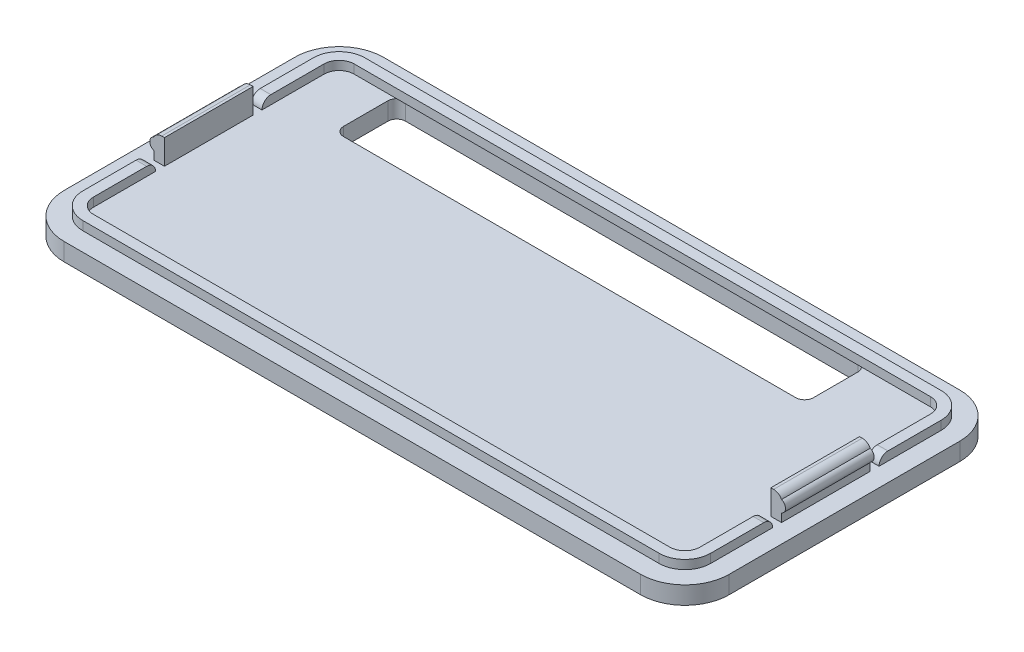
SolidWorks part; units mm, degrees
ref_plane "前视基准面" through (0, 0, 0) normal (0, 0, 1) x (1, 0, 0)
ref_plane "上视基准面" through (0, 0, 0) normal (0, 1, 0) x (1, 0, 0)
ref_plane "右视基准面" through (0, 0, 0) normal (1, 0, 0) x (0, 0, -1)
sketch "zero" plane through (0, 0, 0) normal (0, 1, 0) x (1, 0, 0)
  line L1 (-29.5, 15) -> (29.5, 15)
  line L2 (-32.5, 12) -> (-32.5, -12)
  line L3 (-29.5, -15) -> (29.5, -15)
  line L4 (32.5, 12) -> (32.5, -12)
  line L5 (-32.5, 15) -> (32.5, -15) construction
  line L6 (-32.5, -15) -> (32.5, 15) construction
  line L7 (-25.7, -15) -> (-14.5, -15)
  line L8 (-25.7, -15) -> (-25.7, -9.6569)
  line L9 (-25.7, -9.6569) -> (-14.5, -9.6569)
  line L10 (-14.5, -15) -> (-14.5, -9.6569)
  line L11 (5.2, -15) -> (12.7, -15)
  line L12 (5.2, -15) -> (5.2, -11)
  line L13 (5.2, -11) -> (12.7, -11)
  line L14 (12.7, -15) -> (12.7, -11)
  line L15 (17.8, -15) -> (25.3, -15)
  line L16 (17.8, -15) -> (17.8, -11)
  line L17 (17.8, -11) -> (25.3, -11)
  line L18 (25.3, -15) -> (25.3, -11)
  line L19 (-32.5, 7.7) -> (-19.5, 7.7)
  line L20 (-32.5, 7.7) -> (-32.5, -4.3)
  line L21 (-32.5, -4.3) -> (-19.5, -4.3)
  line L22 (-19.5, 7.7) -> (-19.5, -4.3)
  line L23 (-25.5, 14) -> (25.5, 14)
  line L24 (-25.5, 14) -> (-25.5, 8.8)
  line L25 (-25.5, 8.8) -> (25.5, 8.8)
  line L26 (25.5, 14) -> (25.5, 8.8)
  line L27 (-19.5, 7.2329) -> (-35.5, 7.2329)
  line L28 (-19.5, 7.2329) -> (-19.5, -3.7671)
  line L29 (-19.5, -3.7671) -> (-35.5, -3.7671)
  line L30 (-35.5, 7.2329) -> (-35.5, -3.7671)
  arc A0 (29.5, -15) -> (32.5, -12) centre (29.5, -12) ccw
  arc A1 (29.5, 15) -> (32.5, 12) centre (29.5, 12) cw
  arc A2 (-32.5, -12) -> (-29.5, -15) centre (-29.5, -12) ccw
  arc A3 (-29.5, 15) -> (-32.5, 12) centre (-29.5, 12) ccw
  circle A4 centre (-29, 11.4) radius 3
  circle A5 centre (-29, -11.5) radius 3
  circle A6 centre (29, 11.4) radius 3
  circle A7 centre (29, -11.5) radius 3
  circle A8 centre (-29, 11.4) radius 1.375
  circle A9 centre (-29, -11.5) radius 1.375
  circle A10 centre (29, -11.5) radius 1.375
  circle A11 centre (29, 11.4) radius 1.375
  point P0 (0, 0)
  dimension "D3" = 3
  dimension "D4" = 6
  dimension "D9" = 2.75
  dimension "D1" = 65
  dimension "D2" = 30
  dimension "D5" = 3.6
  dimension "D6" = 3.5
  dimension "D7" = 3.5
  dimension "D8" = 3.5
  dimension "D10" = 12
  dimension "D11" = 7.3
  dimension "D12" = 13
  dimension "D13" = 11.2
  dimension "D14" = 6.8
  dimension "D15" = 19.7
  dimension "D16" = 7.5
  dimension "D17" = 7.5
  dimension "D18" = 5.1
  dimension "D19" = 4
  dimension "D20" = 5.2
  dimension "D21" = 7
  dimension "D22" = 7
  dimension "D23" = 1
  dimension "D24" = 11
  dimension "D25" = 16
sketch "sugar" plane through (0, 0, 0) normal (0, 1, 0) x (1, 0, 0)
  line L1 (-29.5, 15) -> (29.5, 15)
  line L2 (-32.5, 12) -> (-32.5, -12)
  line L3 (-29.5, -15) -> (29.5, -15)
  line L4 (32.5, 12) -> (32.5, -12)
  line L5 (-32.5, 15) -> (32.5, -15) construction
  line L6 (-32.5, -15) -> (32.5, 15) construction
  line L7 (23.5, -11.5) -> (19.5, -11.5)
  line L8 (23.5, -11.5) -> (23.5, -13.9082)
  line L9 (23.5, -13.9082) -> (19.5, -13.9082)
  line L10 (19.5, -11.5) -> (19.5, -13.9082)
  line L11 (16, -11.0071) -> (8.5, -11.0071)
  line L12 (16, -11.0071) -> (16, -15)
  line L13 (16, -15) -> (8.5, -15)
  line L14 (8.5, -11.0071) -> (8.5, -15)
  line L15 (20.5, -13.9082) -> (22.5, -13.9082)
  line L16 (20.5, -13.9082) -> (20.5, -14.8173)
  line L17 (20.5, -14.8173) -> (22.5, -14.8173)
  line L18 (22.5, -13.9082) -> (22.5, -14.8173)
  arc A0 (29.5, 15) -> (32.5, 12) centre (29.5, 12) cw
  arc A1 (29.5, -15) -> (32.5, -12) centre (29.5, -12) ccw
  arc A2 (-32.5, -12) -> (-29.5, -15) centre (-29.5, -12) ccw
  arc A3 (-29.5, 15) -> (-32.5, 12) centre (-29.5, 12) ccw
  circle A4 centre (-29, 11.4) radius 3
  circle A5 centre (-29, 11.4) radius 1.375
  circle A6 centre (-29, -11.5) radius 3
  circle A7 centre (-29, -11.5) radius 1.375
  circle A8 centre (29, 11.4) radius 3
  circle A9 centre (29, 11.4) radius 1.375
  circle A10 centre (29, -11.5) radius 3
  circle A11 centre (29, -11.5) radius 1.375
  dimension "D3" = 3
  dimension "D1" = 65
  dimension "D2" = 30
  dimension "D4" = 9
  dimension "D5" = 4
  dimension "D6" = 3.5
  dimension "D7" = 7.5
  dimension "D8" = 2
  dimension "D9" = 1
sketch "case" plane through (0, 0, 0) normal (0, 1, 0) x (1, 0, 0)
  line L1 (-34.0422, 18) -> (30.9578, 18)
  line L2 (-39.0422, 13) -> (-39.0422, -13)
  line L3 (-34.0422, -18) -> (30.9578, -18)
  line L4 (35.9578, 13) -> (35.9578, -13)
  line L5 (-39.0422, 18) -> (35.9578, -18) construction
  line L6 (-39.0422, -18) -> (35.9578, 18) construction
  arc A0 (-39.0422, -13) -> (-34.0422, -18) centre (-34.0422, -13) ccw
  arc A1 (30.9578, -18) -> (35.9578, -13) centre (30.9578, -13) ccw
  arc A2 (30.9578, 18) -> (35.9578, 13) centre (30.9578, 13) cw
  arc A3 (-34.0422, 18) -> (-39.0422, 13) centre (-34.0422, 13) ccw
  point P0 (-1.5422, 0)
  point P3 (-1.5422, 0)
  dimension "D3" = 5
  dimension "D1" = 75
  dimension "D2" = 36
extrude "凸台-拉伸2" add sketch "case" along normal blind 2
sketch "草图2" plane through (0, 0, 0) normal (0, 1, 0) x (1, 0, 0)
  line L4 (-34.0422, -14.7) -> (30.9578, -14.7)
  line L5 (32.6578, -13) -> (32.6578, 13)
  line L6 (30.9578, 14.7) -> (-34.0422, 14.7)
  line L7 (-35.7422, 13) -> (-35.7422, -13)
  line L8 (33.8578, -13) -> (33.8578, 13)
  line L9 (30.9578, 15.9) -> (-34.0422, 15.9)
  line L10 (-36.9422, 13) -> (-36.9422, -13)
  line L11 (-34.0422, -15.9) -> (30.9578, -15.9)
  line L12 (33.8578, -13) -> (33.8578, 13)
  line L13 (30.9578, 15.9) -> (-34.0422, 15.9)
  line L14 (-36.9422, 13) -> (-36.9422, -13)
  line L15 (-34.0422, -15.9) -> (30.9578, -15.9)
  arc A4 (30.9578, -14.7) -> (32.6578, -13) centre (30.9578, -13) ccw
  arc A5 (32.6578, 13) -> (30.9578, 14.7) centre (30.9578, 13) ccw
  arc A6 (-34.0422, 14.7) -> (-35.7422, 13) centre (-34.0422, 13) ccw
  arc A7 (-35.7422, -13) -> (-34.0422, -14.7) centre (-34.0422, -13) ccw
  arc A8 (30.9578, -15.9) -> (33.8578, -13) centre (30.9578, -13) ccw
  arc A9 (33.8578, 13) -> (30.9578, 15.9) centre (30.9578, 13) ccw
  arc A10 (-34.0422, 15.9) -> (-36.9422, 13) centre (-34.0422, 13) ccw
  arc A11 (-36.9422, -13) -> (-34.0422, -15.9) centre (-34.0422, -13) ccw
  arc A12 (30.9578, -15.9) -> (33.8578, -13) centre (30.9578, -13) ccw
  arc A13 (33.8578, 13) -> (30.9578, 15.9) centre (30.9578, 13) ccw
  arc A14 (-34.0422, 15.9) -> (-36.9422, 13) centre (-34.0422, 13) ccw
  arc A15 (-36.9422, -13) -> (-34.0422, -15.9) centre (-34.0422, -13) ccw
  dimension "D1" = 2.1
  dimension "D2" = 1.2
ref_plane "基准面1" through (0, 2, 0) normal (0, 1, 0) x (1, 0, 0)
sketch "草图3" plane through (0, 2, 0) normal (0, 1, 0) x (1, 0, 0)
  line L4 (-34.0422, -14.7) -> (30.9578, -14.7)
  line L5 (32.6578, -13) -> (32.6578, 13)
  line L6 (30.9578, 14.7) -> (-34.0422, 14.7)
  line L7 (-35.7422, 13) -> (-35.7422, -13)
  line L8 (-34.0422, -14.7) -> (30.9578, -14.7)
  line L9 (32.6578, -13) -> (32.6578, 13)
  line L10 (30.9578, 14.7) -> (-34.0422, 14.7)
  line L11 (-35.7422, 13) -> (-35.7422, -13)
  line L12 (-36.9422, 13) -> (-36.9422, -13)
  line L13 (-34.0422, -15.9) -> (30.9578, -15.9)
  line L14 (33.8578, -13) -> (33.8578, 13)
  line L15 (30.9578, 15.9) -> (-34.0422, 15.9)
  line L16 (-36.9422, 13) -> (-36.9422, -13)
  line L17 (-34.0422, -15.9) -> (30.9578, -15.9)
  line L18 (33.8578, -13) -> (33.8578, 13)
  line L19 (30.9578, 15.9) -> (-34.0422, 15.9)
  arc A4 (30.9578, -14.7) -> (32.6578, -13) centre (30.9578, -13) ccw
  arc A5 (32.6578, 13) -> (30.9578, 14.7) centre (30.9578, 13) ccw
  arc A6 (-34.0422, 14.7) -> (-35.7422, 13) centre (-34.0422, 13) ccw
  arc A7 (-35.7422, -13) -> (-34.0422, -14.7) centre (-34.0422, -13) ccw
  arc A8 (30.9578, -14.7) -> (32.6578, -13) centre (30.9578, -13) ccw
  arc A9 (32.6578, 13) -> (30.9578, 14.7) centre (30.9578, 13) ccw
  arc A10 (-34.0422, 14.7) -> (-35.7422, 13) centre (-34.0422, 13) ccw
  arc A11 (-35.7422, -13) -> (-34.0422, -14.7) centre (-34.0422, -13) ccw
  arc A12 (-36.9422, -13) -> (-34.0422, -15.9) centre (-34.0422, -13) ccw
  arc A13 (30.9578, -15.9) -> (33.8578, -13) centre (30.9578, -13) ccw
  arc A14 (33.8578, 13) -> (30.9578, 15.9) centre (30.9578, 13) ccw
  arc A15 (-34.0422, 15.9) -> (-36.9422, 13) centre (-34.0422, 13) ccw
  arc A16 (-36.9422, -13) -> (-34.0422, -15.9) centre (-34.0422, -13) ccw
  arc A17 (30.9578, -15.9) -> (33.8578, -13) centre (30.9578, -13) ccw
  arc A18 (33.8578, 13) -> (30.9578, 15.9) centre (30.9578, 13) ccw
  arc A19 (-34.0422, 15.9) -> (-36.9422, 13) centre (-34.0422, 13) ccw
  dimension "D1" = 0
  dimension "D2" = 0
extrude "凸台-拉伸4" add sketch "草图3" along normal blind 1
ref_plane "基准面3" through (33.8578, 0, 0) normal (1, 0, 0) x (0, 0, -1)
sketch "草图7" plane through (0, 2, 0) normal (0, 1, 0) x (1, 0, 0)
  line L0 (-36.9422, 13) -> (-36.9422, -13) construction
  line L1 (-36.9422, 5) -> (-35.7422, 5)
  line L2 (-36.9422, 5) -> (-36.9422, -5)
  line L3 (-36.9422, -5) -> (-35.7422, -5)
  line L4 (-35.7422, 5) -> (-35.7422, -5)
  line L5 (-35.7422, 13) -> (-35.7422, -13) construction
  point P10 (-35.7422, 0)
  dimension "D1" = 5
  dimension "D2" = 10
extrude "凸台-拉伸8" add sketch "草图7" along normal blind 2.8
ref_plane "基准面5" through (0, 0, 5) normal (0, 0, 1) x (1, 0, 0)
sketch "草图8" plane through (0, 0, 5) normal (0, 0, 1) x (1, 0, 0)
  line L0 (-34.0422, 2) -> (-39.0422, 2) construction
  line L1 (-36.9422, 4.8) -> (-36.9422, 3) construction
  circle A0 centre (-36.6922, 3.6) radius 0.7
  dimension "D1" = 1.4
  dimension "D2" = 1.6
  dimension "D3" = 0.25
extrude "凸台-拉伸9" add sketch "草图8" against normal blind 10
fillet "圆角1" radius 1 1 edges at (-36.9422, 4.8, 0)
ref_plane "基准面7" through (-36.9422, 0, 0) normal (-1, 0, 0) x (0, 0, 1)
sketch "草图11" plane through (-36.9422, 0, 0) normal (-1, 0, 0) x (0, 0, 1)
  line L0 (-13, 2) -> (13, 2) construction
  line L1 (5, 3) -> (6, 3)
  line L2 (5, 3) -> (5, 2)
  line L3 (5, 2) -> (6, 2)
  line L4 (6, 3) -> (6, 2)
  line L6 (-5, 3) -> (-6, 3)
  line L7 (-5, 3) -> (-5, 2)
  line L8 (-5, 2) -> (-6, 2)
  line L9 (-6, 3) -> (-6, 2)
  dimension "D1" = 1
  dimension "D2" = 1
extrude "切除-拉伸1" cut sketch "草图11" against normal blind 1.2
fillet "圆角2" radius 1 2 edges at (-36.3422, 3, 6) (-36.3422, 3, -6)
ref_plane "基准面8" through (0, 0, 0) normal (0, -1, 0) x (-1, 0, 0)
sketch "草图12" plane through (0, 0, 0) normal (0, -1, 0) x (-1, 0, 0)
  line L76 (34.0422, -18) -> (-30.9578, -18) construction
  line L78 (39.0422, 13) -> (39.0422, -13) construction
  line B0 (-8.1993, 1.426) -> (-9.0198, 1.899)
  line B1 (-9.0198, 1.899) -> (-13.2767, 4.3551)
  line B2 (-13.2767, 4.3551) -> (-14.0973, 4.8339)
  line B3 (-15.8183, 4.8339) -> (-16.6389, 4.3551)
  line B4 (-16.6389, 4.3551) -> (-20.8958, 1.899)
  line B5 (-20.8958, 1.899) -> (-21.7165, 1.426)
  line B6 (-22.577, -0.0613) -> (-22.577, -6.8769)
  line B7 (-21.7165, -8.3643) -> (-20.8958, -8.8373)
  line B8 (-20.8958, -8.8373) -> (-16.6389, -11.2934)
  line B9 (-16.6389, -11.2934) -> (-15.8183, -11.772)
  line B10 (-14.0973, -11.772) -> (-13.2767, -11.2934)
  line B11 (-13.2767, -11.2934) -> (-9.0198, -8.8373)
  line B12 (-9.0198, -8.8373) -> (-8.1993, -8.3643)
  line B13 (-7.3388, -6.8769) -> (-7.3388, -0.0613)
  line B14 (-20.6223, 0.7479) -> (-15.3568, 3.791)
  line B15 (-14.5532, 3.791) -> (-9.3162, 0.7422)
  line B16 (-9.3105, 0.0413) -> (-14.3993, -3.0018)
  line B17 (-12.8208, -8.1591) -> (-13.4135, -8.4896)
  line B18 (-13.4705, -8.5865) -> (-13.4705, -10.2961)
  line B19 (-13.5274, -10.393) -> (-14.633, -11.0198)
  line B20 (-14.7983, -10.9229) -> (-14.7983, -5.646)
  line B21 (-14.7413, -5.5491) -> (-12.8607, -4.4835)
  line B22 (-8.9173, -7.8058) -> (-10.0114, -8.4269)
  line B23 (-10.1767, -8.3301) -> (-10.1767, -5.8169)
  line B24 (-10.1197, -5.7201) -> (-9.0256, -5.1046)
  line B25 (-8.8603, -5.2015) -> (-8.8603, -7.7089)
  line B26 (-12.8893, -7.1447) -> (-13.4135, -7.4069)
  line B27 (-13.4705, -7.2872) -> (-13.4705, -5.9423)
  line B28 (-13.4135, -5.8455) -> (-12.9234, -5.5719)
  line B29 (-3.344, -0.54) -> (-5.2189, -0.54)
  line B30 (-5.2189, -0.54) -> (-5.2189, -7.1048)
  line B31 (-5.2189, -7.1048) -> (-4.3868, -7.1048)
  line B32 (-4.3868, -7.1048) -> (-4.3868, -4.5005)
  line B33 (-4.3868, -4.5005) -> (-3.2984, -4.5005)
  line B34 (-3.4066, -3.8281) -> (-4.3868, -3.8281)
  line B35 (-4.3868, -3.8281) -> (-4.3868, -1.2124)
  line B36 (-4.3868, -1.2124) -> (-3.4408, -1.2124)
  line B37 (0.1948, -2.2382) -> (0.1948, -7.1048)
  line B38 (0.1948, -7.1048) -> (1.0098, -7.1048)
  line B39 (1.0098, -7.1048) -> (1.0098, -2.2382)
  line B40 (1.0098, -2.2382) -> (0.1948, -2.2382)
  line B41 (5.7169, -3.3153) -> (4.8849, -2.9847)
  line B42 (6.0417, -2.1983) -> (6.8396, -1.1953)
  line B43 (3.6084, -4.1586) -> (4.4575, -4.5177)
  line B44 (2.9074, -5.1673) -> (2.0014, -6.2729)
  line B45 (10.8229, -2.0102) -> (10.8229, -5.3497)
  line B46 (9.3811, -4.9621) -> (9.3811, -2.0102)
  line B47 (9.3811, -2.0102) -> (7.7912, -2.0102)
  line B48 (7.7912, -2.0102) -> (7.7912, -5.1616)
  line B49 (10.9711, -6.4039) -> (11.0052, -6.4039)
  line B50 (11.0052, -6.4039) -> (11.1193, -7.1048)
  line B51 (11.1193, -7.1048) -> (12.4185, -7.1048)
  line B52 (12.4185, -7.1048) -> (12.4185, -2.0102)
  line B53 (12.4185, -2.0102) -> (10.8229, -2.0102)
  line B54 (16.2708, -6.1019) -> (15.4673, -6.1019)
  line B55 (17.365, -3.1614) -> (18.1513, -3.1614)
  line B56 (18.1513, -3.1614) -> (18.1513, -2.0102)
  line B57 (18.1513, -2.0102) -> (16.2822, -2.0102)
  line B58 (14.0312, -5.0533) -> (14.0312, -5.0875)
  line B59 (13.9344, -6.9168) -> (13.9344, -6.9624)
  line B60 (15.4844, -7.3214) -> (15.9688, -7.3214)
  line B61 (18.6072, -2.5516) -> (19.1657, -3.6002)
  line B62 (21.411, -6.592) -> (21.4508, -6.592)
  line B63 (21.4508, -6.592) -> (21.5648, -7.1048)
  line B64 (21.5648, -7.1048) -> (22.8641, -7.1048)
  line B65 (22.8641, -7.1048) -> (22.8641, -4.2099)
  line B66 (21.2685, -4.7741) -> (21.2685, -5.589)
  line B67 (25.3545, -2.8935) -> (25.3203, -2.8935)
  line B68 (25.3203, -2.8935) -> (25.212, -2.0102)
  line B69 (25.212, -2.0102) -> (23.9127, -2.0102)
  line B70 (23.9127, -2.0102) -> (23.9127, -7.1048)
  line B71 (23.9127, -7.1048) -> (25.4969, -7.1048)
  line B72 (25.4969, -7.1048) -> (25.4969, -4.1928)
  line B73 (27.1552, -3.3608) -> (27.423, -1.9875)
  line B74 (-13.4135, -7.4069) -> (-13.4135, -8.4896)
  line B75 (-13.4705, -7.2872) -> (-13.4705, -8.5865)
  spline B76 degree 3 poles (-14.0973, 4.8339) (-14.3652, 4.982) (-14.6615, 5.0618) (-14.9578, 5.0618) knots 3 3 3 3 4 4 4 4
  spline B77 degree 3 poles (-14.9578, 5.0618) (-15.2541, 5.0618) (-15.5505, 4.982) (-15.8183, 4.8339) knots 4 4 4 4 5 5 5 5
  spline B78 degree 3 poles (-21.7165, 1.426) (-22.2464, 1.1183) (-22.577, 0.5485) (-22.577, -0.0613) knots 8 8 8 8 9 9 9 9
  spline B79 degree 3 poles (-22.577, -6.8769) (-22.577, -7.4923) (-22.2464, -8.0565) (-21.7165, -8.3643) knots 10 10 10 10 11 11 11 11
  spline B80 degree 3 poles (-15.8183, -11.772) (-15.5505, -11.9259) (-15.2541, -12) (-14.9578, -12) knots 14 14 14 14 15 15 15 15
  spline B81 degree 3 poles (-14.9578, -12) (-14.6615, -12) (-14.3652, -11.9259) (-14.0973, -11.772) knots 15 15 15 15 16 16 16 16
  spline B82 degree 3 poles (-8.1993, -8.3643) (-7.6636, -8.0565) (-7.3388, -7.4923) (-7.3388, -6.8769) knots 19 19 19 19 20 20 20 20
  spline B83 degree 3 poles (-7.3388, -0.0613) (-7.3388, 0.5485) (-7.6636, 1.1183) (-8.1993, 1.426) knots 21 21 21 21 22 22 22 22
  spline B84 degree 2 poles (-15.5106, -3.0018) (-20.6622, -0.0271) (-20.6736, -0.0214) knots 0 0 0 1 1 1
  spline B85 degree 3 poles (-20.6736, -0.0214) (-20.9414, 0.1723) (-20.9129, 0.5826) (-20.6223, 0.7479) knots 1 1 1 1 2 2 2 2
  spline B86 degree 3 poles (-15.3568, 3.791) (-15.1117, 3.9335) (-14.8039, 3.9335) (-14.5532, 3.791) knots 3 3 3 3 4 4 4 4
  spline B87 degree 3 poles (-9.3162, 0.7422) (-9.0484, 0.5883) (-9.0427, 0.2008) (-9.3105, 0.0413) knots 5 5 5 5 6 6 6 6
  spline B88 degree 3 poles (-14.3993, -3.0018) (-14.7413, -3.2013) (-15.1687, -3.2013) (-15.5106, -3.0018) knots 7 7 7 7 8 8 8 8
  spline B89 degree 3 poles (-13.4705, -10.2961) (-13.4705, -10.336) (-13.4876, -10.3702) (-13.5274, -10.393) knots 3 3 3 3 4 4 4 4
  spline B90 degree 3 poles (-14.633, -11.0198) (-14.7071, -11.0597) (-14.7983, -11.0084) (-14.7983, -10.9229) knots 5 5 5 5 6 6 6 6
  spline B91 degree 3 poles (-14.7983, -5.646) (-14.7983, -5.6061) (-14.7812, -5.5662) (-14.7413, -5.5491) knots 7 7 7 7 8 8 8 8
  spline B92 degree 3 poles (-12.8607, -4.4835) (-11.6412, -3.7939) (-10.6326, -3.6572) (-10.6326, -5.0249) knots 9 9 9 9 10 10 10 10
  spline B93 degree 3 poles (-10.6326, -5.0249) (-10.6326, -6.3412) (-11.6526, -7.498) (-12.8208, -8.1591) knots 10 10 10 10 11 11 11 11
  spline B94 degree 3 poles (-8.8603, -7.7089) (-8.8603, -7.7488) (-8.8831, -7.7887) (-8.9173, -7.8058) knots 0 0 0 0 1 1 1 1
  spline B95 degree 3 poles (-10.0114, -8.4269) (-10.0855, -8.4668) (-10.1767, -8.4155) (-10.1767, -8.3301) knots 2 2 2 2 3 3 3 3
  spline B96 degree 3 poles (-10.1767, -5.8169) (-10.1767, -5.7771) (-10.1539, -5.7429) (-10.1197, -5.7201) knots 4 4 4 4 5 5 5 5
  spline B97 degree 3 poles (-9.0256, -5.1046) (-8.9515, -5.0647) (-8.8603, -5.116) (-8.8603, -5.2015) knots 6 6 6 6 7 7 7 7
  spline B98 degree 3 poles (-9.5156, -3.4349) (-9.0768, -3.1842) (-8.7634, -3.2924) (-8.7634, -3.6914) (-8.7634, -4.0846) (-9.0768, -4.5461) (-9.5156, -4.7912) knots 2 2 2 2 3 3 3 4 4 4 4
  spline B99 degree 3 poles (-9.5156, -4.7912) (-9.9601, -5.0476) (-10.2735, -4.9394) (-10.2735, -4.5461) (-10.2735, -4.1415) (-9.9601, -3.6856) (-9.5156, -3.4349) knots 0 0 0 0 1 1 1 2 2 2 2
  spline B100 degree 3 poles (-11.9319, -5.76) (-11.9319, -6.3013) (-12.2395, -6.78) (-12.8893, -7.1447) knots 0 0 0 0 1 1 1 1
  spline B101 degree 3 poles (-13.4705, -5.9423) (-13.4705, -5.9024) (-13.4477, -5.8625) (-13.4135, -5.8455) knots 4 4 4 4 5 5 5 5
  spline B102 degree 3 poles (-12.9234, -5.5719) (-12.2852, -5.2072) (-11.9319, -5.2015) (-11.9319, -5.76) knots 6 6 6 6 7 7 7 7
  spline B103 degree 3 poles (-3.2984, -4.5005) (-1.868, -4.5005) (-0.8822, -3.8509) (-0.8822, -2.4661) knots 5 5 5 5 6 6 6 6
  spline B104 degree 3 poles (-0.8822, -2.4661) (-0.8822, -1.0301) (-1.868, -0.54) (-3.344, -0.54) knots 6 6 6 6 7 7 7 7
  spline B105 degree 3 poles (-3.4408, -1.2124) (-2.2897, -1.2124) (-1.7084, -1.5145) (-1.7084, -2.4661) knots 3 3 3 3 4 4 4 4
  spline B106 degree 3 poles (-1.7084, -2.4661) (-1.7084, -3.4064) (-2.2498, -3.8281) (-3.4066, -3.8281) knots 4 4 4 4 5 5 5 5
  spline B107 degree 3 poles (0.6052, -1.2352) (0.93, -1.2352) (1.1694, -1.013) (1.1694, -0.711) (1.1694, -0.3747) (0.93, -0.181) (0.6052, -0.181) knots 2 2 2 2 3 3 3 4 4 4 4
  spline B108 degree 3 poles (0.6052, -0.181) (0.2804, -0.181) (0.041, -0.3747) (0.041, -0.711) (0.041, -1.013) (0.2804, -1.2352) (0.6052, -1.2352) knots 0 0 0 0 1 1 1 2 2 2 2
  spline B109 degree 3 poles (4.8849, -2.9847) (4.2979, -2.7511) (3.8762, -2.6086) (3.8762, -2.2382) knots 1 1 1 1 2 2 2 2
  spline B110 degree 3 poles (3.8762, -2.2382) (3.8762, -1.8849) (4.1783, -1.6854) (4.674, -1.6854) knots 2 2 2 2 3 3 3 3
  spline B111 degree 3 poles (4.674, -1.6854) (5.1926, -1.6854) (5.6029, -1.8621) (6.0417, -2.1983) knots 3 3 3 3 4 4 4 4
  spline B112 degree 3 poles (6.8396, -1.1953) (6.2583, -0.6084) (5.4433, -0.3121) (4.674, -0.3121) knots 5 5 5 5 6 6 6 6
  spline B113 degree 3 poles (4.674, -0.3121) (3.2551, -0.3121) (2.2521, -1.2124) (2.2521, -2.3294) knots 6 6 6 6 7 7 7 7
  spline B114 degree 3 poles (2.2521, -2.3294) (2.2521, -3.2981) (2.9074, -3.8794) (3.6084, -4.1586) knots 7 7 7 7 8 8 8 8
  spline B115 degree 3 poles (4.4575, -4.5177) (5.0274, -4.757) (5.3978, -4.8824) (5.3978, -5.2699) knots 9 9 9 9 10 10 10 10
  spline B116 degree 3 poles (5.3978, -5.2699) (5.3978, -5.6289) (5.1185, -5.8511) (4.5259, -5.8511) knots 10 10 10 10 11 11 11 11
  spline B117 degree 3 poles (4.5259, -5.8511) (4.0016, -5.8511) (3.3804, -5.5719) (2.9074, -5.1673) knots 11 11 11 11 12 12 12 12
  spline B118 degree 3 poles (2.0014, -6.2729) (2.6909, -6.9054) (3.6254, -7.2302) (4.4916, -7.2302) knots 13 13 13 13 14 14 14 14
  spline B119 degree 3 poles (4.4916, -7.2302) (6.1044, -7.2302) (7.0389, -6.2557) (7.0389, -5.1445) knots 14 14 14 14 15 15 15 15
  spline B120 degree 3 poles (7.0389, -5.1445) (7.0389, -4.2042) (6.5432, -3.6458) (5.7169, -3.3153) knots 15 15 15 15 16 16 16 16
  spline B121 degree 3 poles (10.8229, -5.3497) (10.5551, -5.7258) (10.3328, -5.8682) (9.9738, -5.8682) knots 1 1 1 1 2 2 2 2
  spline B122 degree 3 poles (9.9738, -5.8682) (9.5692, -5.8682) (9.3811, -5.6688) (9.3811, -4.9621) knots 2 2 2 2 3 3 3 3
  spline B123 degree 3 poles (7.7912, -5.1616) (7.7912, -6.4324) (8.2642, -7.2302) (9.3754, -7.2302) knots 6 6 6 6 7 7 7 7
  spline B124 degree 3 poles (9.3754, -7.2302) (10.0706, -7.2302) (10.5494, -6.9054) (10.9711, -6.4039) knots 7 7 7 7 8 8 8 8
  spline B125 degree 3 poles (15.4673, -6.1019) (14.9202, -6.1019) (14.7151, -5.9936) (14.7151, -5.76) knots 1 1 1 1 2 2 2 2
  spline B126 degree 3 poles (14.7151, -5.76) (14.7151, -5.589) (14.7549, -5.5092) (14.8746, -5.4009) knots 2 2 2 2 3 3 3 3
  spline B127 degree 3 poles (14.8746, -5.4009) (15.0969, -5.4636) (15.302, -5.4921) (15.473, -5.4921) knots 3 3 3 3 4 4 4 4
  spline B128 degree 3 poles (15.473, -5.4921) (16.6013, -5.4921) (17.5074, -4.9735) (17.5074, -3.7825) knots 4 4 4 4 5 5 5 5
  spline B129 degree 3 poles (17.5074, -3.7825) (17.5074, -3.5375) (17.4447, -3.3038) (17.365, -3.1614) knots 5 5 5 5 6 6 6 6
  spline B130 degree 3 poles (16.2822, -2.0102) (16.0485, -1.9248) (15.7693, -1.8849) (15.473, -1.8849) knots 9 9 9 9 10 10 10 10
  spline B131 degree 3 poles (15.473, -1.8849) (14.3732, -1.8849) (13.3417, -2.4889) (13.3417, -3.7369) knots 10 10 10 10 11 11 11 11
  spline B132 degree 3 poles (13.3417, -3.7369) (13.3417, -4.3296) (13.6722, -4.8026) (14.0312, -5.0533) knots 11 11 11 11 12 12 12 12
  spline B133 degree 3 poles (14.0312, -5.0875) (13.7007, -5.3212) (13.467, -5.6802) (13.467, -6.0392) knots 13 13 13 13 14 14 14 14
  spline B134 degree 3 poles (13.467, -6.0392) (13.467, -6.4666) (13.6665, -6.7344) (13.9344, -6.9168) knots 14 14 14 14 15 15 15 15
  spline B135 degree 3 poles (13.9344, -6.9624) (13.4613, -7.2017) (13.2106, -7.5436) (13.2106, -7.9653) knots 16 16 16 16 17 17 17 17
  spline B136 degree 3 poles (13.2106, -7.9653) (13.2106, -8.8771) (14.1737, -9.2475) (15.3476, -9.2475) knots 17 17 17 17 18 18 18 18
  spline B137 degree 3 poles (15.3476, -9.2475) (17.1199, -9.2475) (18.2312, -8.4839) (18.2312, -7.4069) knots 18 18 18 18 19 19 19 19
  spline B138 degree 3 poles (18.2312, -7.4069) (18.2312, -6.4837) (17.5245, -6.1019) (16.2708, -6.1019) knots 19 19 19 19 20 20 20 20
  spline B139 degree 3 poles (15.473, -4.5347) (15.1083, -4.5347) (14.8291, -4.2669) (14.8291, -3.7369) (14.8291, -3.2184) (15.1083, -2.9505) (15.473, -2.9505) knots 2 2 2 2 3 3 3 4 4 4 4
  spline B140 degree 3 poles (15.473, -2.9505) (15.8491, -2.9505) (16.1169, -3.2184) (16.1169, -3.7369) (16.1169, -4.2669) (15.8491, -4.5347) (15.473, -4.5347) knots 0 0 0 0 1 1 1 2 2 2 2
  spline B141 degree 3 poles (15.5983, -8.2503) (14.943, -8.2503) (14.5156, -8.0736) (14.5156, -7.7146) knots 0 0 0 0 1 1 1 1
  spline B142 degree 3 poles (14.5156, -7.7146) (14.5156, -7.5436) (14.5953, -7.4012) (14.7549, -7.2587) knots 1 1 1 1 2 2 2 2
  spline B143 degree 3 poles (14.7549, -7.2587) (14.9202, -7.3043) (15.114, -7.3214) (15.4844, -7.3214) knots 2 2 2 2 3 3 3 3
  spline B144 degree 3 poles (15.9688, -7.3214) (16.4417, -7.3214) (16.7096, -7.3841) (16.7096, -7.6861) knots 4 4 4 4 5 5 5 5
  spline B145 degree 3 poles (16.7096, -7.6861) (16.7096, -8.0109) (16.2537, -8.2503) (15.5983, -8.2503) knots 5 5 5 5 6 6 6 6
  spline B146 degree 3 poles (20.8013, -1.8849) (20.0091, -1.8849) (19.2797, -2.1527) (18.6072, -2.5516) knots 0 0 0 0 1 1 1 1
  spline B147 degree 3 poles (19.1657, -3.6002) (19.6729, -3.3153) (20.0946, -3.1557) (20.4992, -3.1557) knots 2 2 2 2 3 3 3 3
  spline B148 degree 3 poles (20.4992, -3.1557) (21.0177, -3.1557) (21.2344, -3.395) (21.2685, -3.8053) knots 3 3 3 3 4 4 4 4
  spline B149 degree 3 poles (21.2685, -3.8053) (19.2797, -4.0219) (18.4362, -4.6031) (18.4362, -5.6802) knots 4 4 4 4 5 5 5 5
  spline B150 degree 3 poles (18.4362, -5.6802) (18.4362, -6.5293) (19.0118, -7.2302) (19.9522, -7.2302) knots 5 5 5 5 6 6 6 6
  spline B151 degree 3 poles (19.9522, -7.2302) (20.5163, -7.2302) (20.9893, -6.9681) (21.411, -6.592) knots 6 6 6 6 7 7 7 7
  spline B152 degree 3 poles (22.8641, -4.2099) (22.8641, -2.6143) (22.1176, -1.8849) (20.8013, -1.8849) knots 11 11 11 11 12 12 12 12
  spline B153 degree 3 poles (21.2685, -5.589) (21.0349, -5.8398) (20.824, -5.9936) (20.4992, -5.9936) knots 0 0 0 0 1 1 1 1
  spline B154 degree 3 poles (20.4992, -5.9936) (20.1686, -5.9936) (19.9522, -5.8511) (19.9522, -5.5548) knots 1 1 1 1 2 2 2 2
  spline B155 degree 3 poles (19.9522, -5.5548) (19.9522, -5.1958) (20.277, -4.9109) (21.2685, -4.7741) knots 2 2 2 2 3 3 3 3
  spline B156 degree 3 poles (26.8076, -1.8849) (26.2947, -1.8849) (25.7305, -2.2154) (25.3545, -2.8935) knots 0 0 0 0 1 1 1 1
  spline B157 degree 3 poles (25.4969, -4.1928) (25.7648, -3.5204) (26.2207, -3.2811) (26.5967, -3.2811) knots 7 7 7 7 8 8 8 8
  spline B158 degree 3 poles (26.5967, -3.2811) (26.8247, -3.2811) (26.9729, -3.3153) (27.1552, -3.3608) knots 8 8 8 8 9 9 9 9
  spline B159 degree 3 poles (27.423, -1.9875) (27.2806, -1.9248) (27.1096, -1.8849) (26.8076, -1.8849) knots 10 10 10 10 11 11 11 11
  dimension "D1" = 6
  dimension "D2" = 54
sketch_block_instance "块1-1"
sketch_block "块1"
extrude "切除-拉伸2" cut sketch "草图12" against normal blind 0.5
sketch "草图13" plane through (0, 0, 0) normal (0, 1, 0) x (1, 0, 0)
  line L0 (30.9578, 18) -> (-34.0422, 18) construction
  line L1 (-29.5422, 15) -> (23.4578, 15)
  line L2 (-29.5422, 15) -> (-29.5422, 8)
  line L3 (-29.5422, 8) -> (23.4578, 8)
  line L4 (23.4578, 15) -> (23.4578, 8)
  line L6 (-39.0422, 13) -> (-39.0422, -13) construction
  dimension "D1" = 7
  dimension "D2" = 53
  dimension "D3" = 3
  dimension "D4" = 9.5
extrude "切除-拉伸3" cut sketch "草图13" along normal blind 2
fillet "圆角3" radius 1 4 edges at (-29.5422, 1, -15) (-29.5422, 1, -8) (23.4578, 1, -15) (23.4578, 1, -8)
sketch "草图14" plane through (0, 3, 0) normal (0, 1, 0) x (1, 0, 0)
  line L0 (33.8578, -13) -> (33.8578, 13) construction
  line L1 (33.8578, 5) -> (32.6578, 5)
  line L2 (33.8578, 5) -> (33.8578, -5)
  line L3 (33.8578, -5) -> (32.6578, -5)
  line L4 (32.6578, 5) -> (32.6578, -5)
  line L5 (32.6578, -13) -> (32.6578, 13) construction
  line L6 (35.9578, -13) -> (35.9578, 13) construction
  point P10 (33.8578, 0)
  point P11 (35.9578, 0)
  dimension "D1" = 10
extrude "凸台-拉伸10" add sketch "草图14" along normal blind 1.8
sketch "草图15" plane through (0, 0, -5) normal (0, 0, -1) x (-1, 0, 0)
  line L0 (-30.9578, 2) -> (-35.9578, 2) construction
  line L1 (-33.8578, 4.8) -> (-33.8578, 3) construction
  circle A0 centre (-33.6078, 3.6) radius 0.7
  dimension "D1" = 1.4
  dimension "D2" = 1.6
  dimension "D3" = 0.25
extrude "凸台-拉伸11" add sketch "草图15" against normal blind 10 contours A0
fillet "圆角4" radius 1 1 edges at (33.8578, 4.8, 0)
sketch "草图16" plane through (0, 3, 0) normal (0, 1, 0) x (1, 0, 0)
  line L0 (33.8578, -13) -> (33.8578, -5) construction
  line L1 (32.6578, -5) -> (33.8578, -5)
  line L2 (32.6578, -5) -> (32.6578, -6)
  line L3 (32.6578, -6) -> (33.8578, -6)
  line L4 (33.8578, -5) -> (33.8578, -6)
  line L5 (33.8578, 5) -> (33.8578, 13) construction
  line L6 (32.6578, 5) -> (33.8578, 5)
  line L7 (32.6578, 5) -> (32.6578, 6)
  line L8 (32.6578, 6) -> (33.8578, 6)
  line L9 (33.8578, 5) -> (33.8578, 6)
  dimension "D1" = 1
  dimension "D2" = 1
extrude "切除-拉伸4" cut sketch "草图16" against normal blind 1
fillet "圆角5" radius 1 2 edges at (33.2578, 3, 6) (33.2578, 3, -6)
